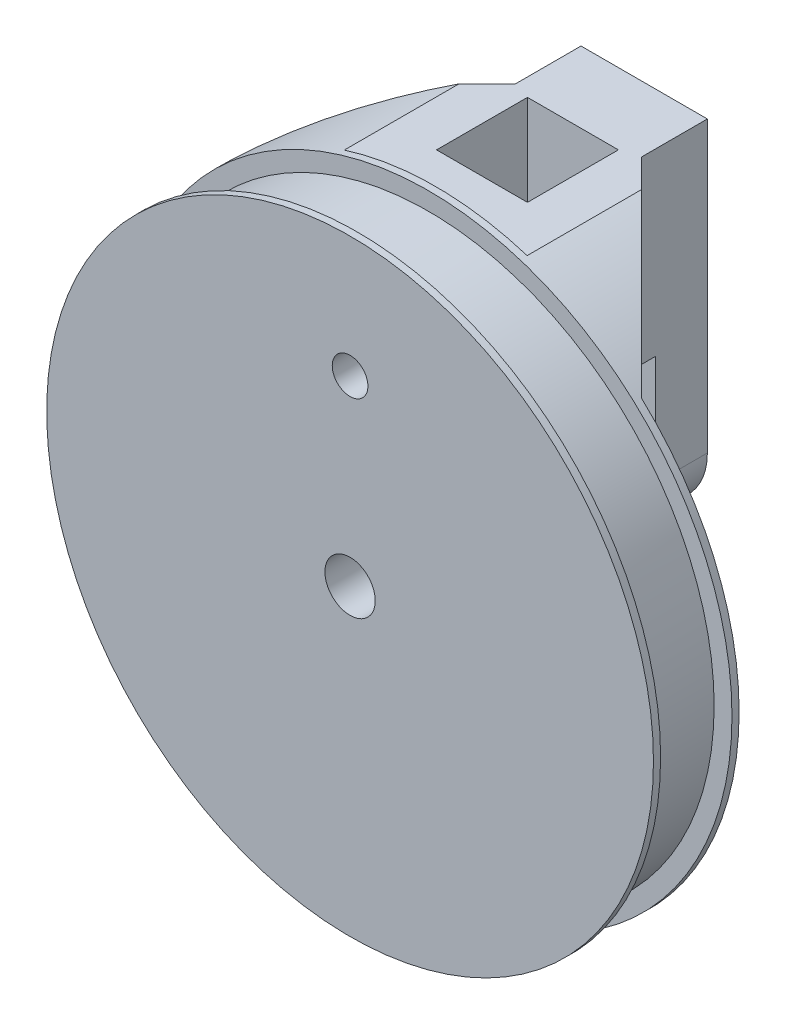
SolidWorks part; units mm, degrees
other "Markup1"
sketch "Sketch12" plane through (-30, -58, 49.7) normal (-0.8709, -0.4905, 0.0319) x (-0.1533, 0.2093, -0.9658)
other "Markup2"
sketch "Sketch14" plane through (30, -60, 49.7) normal (0.6168, -0.7172, 0.3243) x (-0.4689, -0.0038, 0.8832)
material "PETG"
ref_plane "Front Plane" through (0, 0, 0) normal (0, 0, 1) x (1, 0, 0)
ref_plane "Top Plane" through (0, 0, 0) normal (0, 1, 0) x (1, 0, 0)
ref_plane "Right Plane" through (0, 0, 0) normal (1, 0, 0) x (0, 0, -1)
sketch "Sketch1" plane through (0, 0, 0) normal (0, 1, 0) x (1, 0, 0)
  line L1 (-12.7375, -12.7375) -> (12.7375, -12.7375)
  line L2 (-12.7375, -12.7375) -> (-12.7375, 12.7375)
  line L3 (-12.7375, 12.7375) -> (12.7375, 12.7375)
  line L4 (12.7375, -12.7375) -> (12.7375, 12.7375)
  line L5 (-17.7, -17.7) -> (17.7, -17.7)
  line L6 (-17.7, -17.7) -> (-17.7, 17.7)
  line L7 (-17.7, 17.7) -> (17.7, 17.7)
  line L8 (17.7, -17.7) -> (17.7, 17.7)
  point P8 (0, -17.7)
  point P9 (0, -12.7375)
  point P12 (-17.7, 0)
  point P13 (-12.7375, 0)
  dimension "D1" = 25.475
  dimension "D2" = 35.4
extrude "Boss-Extrude1" add sketch "Sketch1" along normal blind 47.0375
extrude "Boss-Extrude2" add sketch "Sketch1<3>" against normal blind 14.9625 contours L1 L4 L3 L2 | L5 L8 L7 L6 L4 L1 L2 L3 region at (0, 0, 0) region at (-17.1994, 0, 0)
sketch "Sketch1<3>" plane through (0, 0, 0) normal (0, 1, 0) x (1, 0, 0) same geometry as "Sketch1"
sketch "Sketch3" plane through (0, 0, 0) normal (0, -1, 0) x (-1, 0, 0)
  circle A0 centre (0, 0) radius 3.15
  dimension "D1" = 6.3
extrude "Cut-Extrude1" cut sketch "Sketch3" along normal through all
sketch "Sketch13" plane through (0, -14.9625, 0) normal (0, -1, 0) x (1, 0, 0)
  circle A0 centre (0, 0) radius 5.5
  dimension "D1" = 11
extrude "Cut-Extrude4" cut sketch "Sketch13" against normal offset from surface (6.9625 mm away) 8 up to face at (0, 0, -3.15)
sketch "Sketch4" plane through (0, 0, 17.7) normal (0, 0, 1) x (1, 0, 0)
  line L0 (17.7, 47.0375) -> (17.7, -14.9625) construction
  line L1 (-17.7, 47.0375) -> (-17.7, -14.9625) construction
  line L2 (17.7, -34.0125) -> (17.7, -14.9625)
  line L3 (-17.7, -34.0125) -> (-17.7, -14.9625)
  line L5 (17.7, 47.0375) -> (-17.7, 47.0375)
  line L6 (17.7, 47.0375) -> (17.7, -14.9625)
  line L8 (-17.7, 47.0375) -> (-17.7, -14.9625)
  line L9 (-17.7, -14.9625) -> (17.7, -14.9625) construction
  line L10 (-17.7, 47.0375) -> (17.7, 47.0375) construction
  arc A0 (-17.7, -34.0125) -> (17.7, -34.0125) centre (0, -34.0125) ccw
  circle A1 centre (0, -34.0125) radius 7.05
  dimension "D2" = 14.1
  dimension "D1" = 19.05
extrude "Boss-Extrude3" add sketch "Sketch4" along normal blind 15
sketch "Sketch6" plane through (0, 0, 17.7) normal (0, 0, -1) x (-1, 0, 0)
  line L0 (17.7, -34.0125) -> (17.7, -14.9625)
  line L1 (17.7, -14.9625) -> (-17.7, -14.9625)
  line L2 (-17.7, -14.9625) -> (-17.7, -34.0125)
  arc A0 (-17.7, -34.0125) -> (17.7, -34.0125) centre (0, -34.0125) ccw
  arc A4 (-17.7, -34.0125) -> (17.7, -34.0125) centre (0, -34.0125) ccw construction
extrude "Cut-Extrude2" cut sketch "Sketch6" against normal blind 0.5375
sketch "Sketch7" plane through (0, 0, 18.2375) normal (0, 0, -1) x (-1, 0, 0)
  circle A0 centre (0, -34.0125) radius 11.0375
  arc A1 (-17.7, -34.0125) -> (17.7, -34.0125) centre (0, -34.0125) ccw construction
  dimension "D1" = 22.075
extrude "Cut-Extrude3" cut sketch "Sketch7" against normal blind 7
mirror "Mirror1" about plane through (0, 0, 0) normal (0, 0, 1) of "Boss-Extrude3", "Cut-Extrude2", "Cut-Extrude1", "Cut-Extrude3"
sketch "Sketch18" plane through (0, 0, 0) normal (0, 0, 1) x (1, 0, 0)
  line L0 (0, -13.5166) -> (-17.7, -3.2975)
  line L1 (-17.7, -3.2975) -> (-35.45, -34.0414) construction
  line L2 (-35.45, -34.0414) -> (-8.875, -49.3845) construction
  line L3 (-17.7, 47.0375) -> (-17.7, -34.0125) construction
  line L4 (0, -35.0322) -> (0, -50035.0322) construction
  line L5 (-17.7, -3.2975) -> (-17.7, -14.9625)
  line L6 (17.7, -34.0125) -> (17.7, 47.0375) construction
  line L7 (17.7, -3.2975) -> (0, -13.5166)
  line L10 (17.7, -14.9625) -> (17.7, -3.2975)
  line L11 (-17.7, -14.9625) -> (17.7, -14.9625)
  line L12 (-5.5, -14.9625) -> (5.5, -14.9625) construction
  circle A0 centre (0, -34.0125) radius 17.75 construction
  arc A2 (-17.7, -34.0125) -> (17.7, -34.0125) centre (0, -34.0125) ccw construction
  dimension "D2" = 120
  dimension "D1" = 35.5
extrude "Cut-Extrude10" cut sketch "Sketch18" along normal up to surface and the other way up to surface up to face at (-11.0375, -34.0125, 18.2375) other way up to face at (-11.0375, -34.0125, -18.2375)
ref_plane "Plane1" through (0, 0, 27.7) normal (0, 0, 1) x (1, 0, 0)
sketch "Sketch9" plane through (0, 0, 27.7) normal (0, 0, 1) x (1, 0, 0)
  circle A0 centre (0, -34.0125) radius 85
  circle A1 centre (0, -34.0125) radius 7.05 construction
  circle A2 centre (0, -34.0125) radius 7.05
  dimension "D1" = 170
extrude "Boss-Extrude4" add sketch "Sketch9" against normal blind 2 contours A0 region at (-82.5958, -34.0125, 27.7)
sketch "Sketch10" plane through (0, 0, 27.7) normal (0, 0, -1) x (-1, 0, 0)
  circle A0 centre (0, -34.0125) radius 80
  circle A1 centre (0, -34.0125) radius 7.05
  circle A2 centre (0, -34.0125) radius 85 construction
  circle A3 centre (0, -34.0125) radius 7.05 construction
  dimension "D1" = 160
extrude "Boss-Extrude5" add sketch "Sketch10" against normal blind 20 contours A0 | A1
extrude "Cut-Extrude7" cut sketch "Sketch10<3>" against normal through all flip side to cut
sketch "Sketch10<3>" plane through (0, 0, 27.7) normal (0, 0, -1) x (-1, 0, 0) same geometry as "Sketch10"
sketch "Sketch11" plane through (0, 0, 47.7) normal (0, 0, 1) x (1, 0, 0)
  circle A0 centre (0, -34.0125) radius 85
  circle A1 centre (0, -34.0125) radius 7.05
  circle A2 centre (0, -34.0125) radius 7.05 construction
  circle A3 centre (0, -34.0125) radius 85 construction
  circle M10 centre (0, -34.0125) radius 7.05
  circle M11 centre (0, -34.0125) radius 80
extrude "Boss-Extrude6" add sketch "Sketch11" along normal blind 2 contours A0 M11 | M11 M10 region at (-82.5958, -34.0125, 47.7) region at (-77.7373, -34.0125, 47.7)
sketch "Sketch15" plane through (0, 0, -32.7) normal (0, 0, -1) x (-1, 0, 0)
  line L1 (0, 17.0375) -> (-17.7, 17.0375) construction
  line L2 (0, 17.0375) -> (17.7, 17.0375) construction
  line L3 (17.7, 47.0375) -> (17.7, -34.0125) construction
  line L4 (-17.7, -34.0125) -> (-17.7, 47.0375) construction
  line L5 (-17.7, 47.0375) -> (17.7, 47.0375) construction
  circle A0 centre (0, 17.0375) radius 2.8
  dimension "D1" = 5.6
  dimension "D2" = 30
extrude "Cut-Extrude5" cut sketch "Sketch15" against normal up to next
sketch "Sketch16" plane through (0, 0, -32.7) normal (0, 0, -1) x (-1, 0, 0)
  circle A0 centre (0, 17.0375) radius 5
  circle A1 centre (0, 17.0375) radius 2.8 construction
  dimension "D1" = 10
extrude "Cut-Extrude6" cut sketch "Sketch16" against normal blind 10 and the other way through all
mirror "Mirror2" about plane through (0, 0, 0) normal (0, 0, 1) of "Cut-Extrude5", "Cut-Extrude6"
sketch "Sketch17" plane through (0, 0, 25.7) normal (0, 0, -1) x (-1, 0, 0)
  line L0 (8.875, -49.3845) -> (80.8643, -7.8214) construction
  line L1 (80.8643, -7.8214) -> (63.1143, 22.9225) construction
  line L2 (63.1143, 22.9225) -> (-8.875, -18.6405) construction
  line L3 (0, -31.0125) -> (0, -50031.0125) construction
  line L4 (17.7, -3.2975) -> (17.7, 47.0375)
  line L5 (17.7, 47.0375) -> (17.7, -34.0125) construction
  line L6 (17.7, 47.0375) -> (17.7, -34.0125) construction
  line L8 (57.7, 28.4031) -> (57.7, 19.7965)
  line L9 (57.7, 19.7965) -> (17.7, -3.2975)
  line L10 (17.7, 47.0375) -> (25.6105, 47.0375)
  circle A0 centre (0, -34.0125) radius 17.75 construction
  circle A1 centre (0, -34.0125) radius 85 construction
  arc A3 (57.7, 28.4031) -> (25.6105, 47.0375) centre (0, -34.0125) ccw
  dimension "D2" = 120
  dimension "D3" = 40
  dimension "D1" = 35.5
extrude "Boss-Extrude7" add sketch "Sketch17" along normal blind 40
chamfer "Chamfer1" distance 40 angle 45 1 edges at (-57.7, 24.0998, -14.3)
mirror "Mirror3" about plane through (0, 0, 0) normal (1, 0, 0) of "Chamfer1", "Boss-Extrude7"
equation "\"tol_dia_id_intfc\" = 0.0500mm ' For hole diameters - Interference fit"
equation "\"tol_dia_id_slip\"  = 0.0750mm ' For hole diameters - Slip fit"
equation "\"tol_dia_id_clear\" = 0.1000mm ' For hole diameters - Clearance fit"
equation "\"tol_dia_od_intfc\" = 0.0500mm ' For shaft diameters - Interference fit"
equation "\"tol_dia_od_slip\"  = 0.0750mm ' For shaft diameters - Slip fit"
equation "\"tol_dia_od_clear\" = 0.1000mm ' For shaft diameters - Clearance fit"
equation "\"tol_general_intfc\"= 0.0250mm ' For general parts (Horiz) - Interference fit"
equation "\"tol_general_slip\" = 0.0375mm ' For general parts (Horiz) - Slip fit"
equation "\"tol_general_clear\"= 0.0500mm ' For general parts (Horiz) - Clearance fit"
equation "\"tol_layer_intfc\"  = 0.0250mm ' For all parts (Vert) - Interference fit"
equation "\"tol_layer_slip\"   = 0.0375mm ' For all parts (Vert) - Slip fit"
equation "\"tol_layer_clear\"  = 0.0500mm ' For all parts (Vert) - Clearance fit"
equation "\"tol_corner_rad\"   = 0.100mm ' For corners that fit into other parts"
equation "\"D1@Sketch1\"= 25.4 + \"tol_general_slip\" * 2"
equation "\"D2@Sketch1\"=25.4+10"
equation "\"D1@Boss-Extrude1\"=47.00mm+\"tol_layer_slip\""
equation "\"D1@Boss-Extrude2\"=15.00mm-\"tol_layer_slip\""
equation "\"D2@Sketch4\"= 14.00mm + \"tol_dia_id_clear\""
equation "\"D1@Sketch4\"= 19.00mm + \"tol_layer_clear\""
equation "\"D1@Sketch7\"= 22.00mm + \"tol_dia_id_slip\""
equation "\"D1@Cut-Extrude2\"=0.50mm+\"tol_general_slip\""
equation "\"pitch_dia\"= 160mm"
equation "\"belt_width\"= 20mm"
equation "\"D1@Boss-Extrude5\"=\"belt_width\""
equation "\"D1@Sketch10\"=\"pitch_dia\""
equation "\"D1@Sketch9\"=\"pitch_dia\"+10.00mm"
equation "\"pulley_chamfer\"= 40mm"
equation "\"D1@Boss-Extrude7\"=\"pulley_chamfer\""
equation "\"D1@Chamfer1\"=\"pulley_chamfer\""
equation "\"D3@Sketch17\"=\"pulley_chamfer\""
equation "\"D1@Sketch17\"=35.40mm+\"tol_general_clear\"*2"
equation "\"D1@Sketch18\"=35.40+\"tol_general_clear\"*2"
